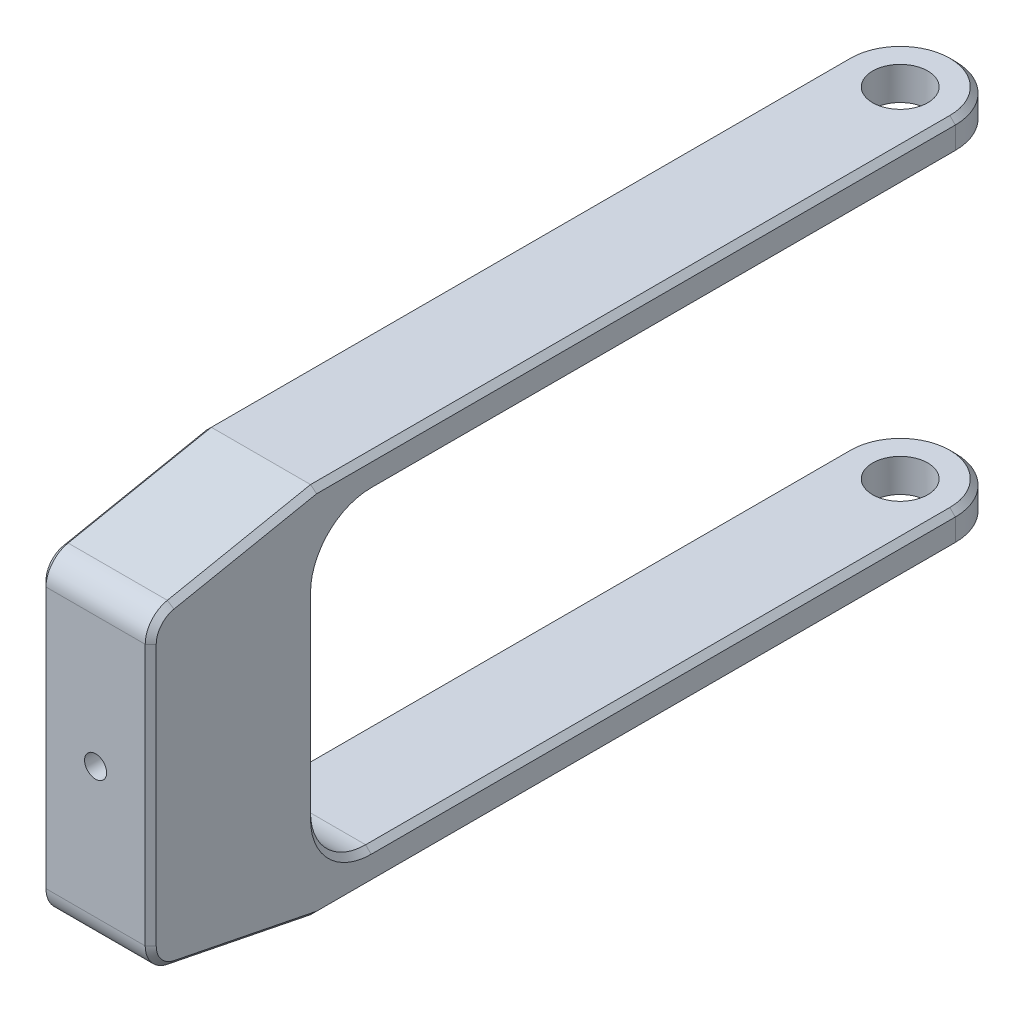
SolidWorks part; units mm, degrees
material "ﾒﾗﾐﾝ樹脂"
ref_plane "正面" through (0, 0, 0) normal (0, 0, 1) x (1, 0, 0)
ref_plane "平面" through (0, 0, 0) normal (0, 1, 0) x (1, 0, 0)
ref_plane "右側面" through (0, 0, 0) normal (1, 0, 0) x (0, 0, -1)
sketch "ｽｹｯﾁ1" plane through (0, 0, 0) normal (0, 1, 0) x (1, 0, 0)
  line L0 (0, 0) -> (0, 63)
  line L1 (0, 63) -> (0, 58)
  line L2 (-5, 58) -> (-5, 0)
  line L3 (-5, 0) -> (5, 0)
  line L4 (5, 0) -> (5, 58)
  line L5 (-5, 58) -> (-5, 63)
  line L6 (-5, 63) -> (0, 63)
  line L7 (0, 63) -> (5, 63)
  line L8 (5, 63) -> (5, 58)
  arc A0 (-5, 58) -> (5, 58) centre (0, 58) cw
extrude "ﾎﾞｽ - 押し出し2" add sketch "ｽｹｯﾁ1" along normal blind 33.8 contours A0 L2 L3 L0 | A0 L0 L3 L4 | L5 A0 L6 | L7 A0 L8 region at (-2.476, 0, -30.9736) region at (2.476, 0, -30.9736) region at (-3.8832, 0, -61.8832) region at (3.8832, 0, -61.8832)
sketch "ｽｹｯﾁ2" plane through (-5, 0, 0) normal (-1, 0, 0) x (0, 0, 1)
  line L0 (-63, 0) -> (-63, 3)
  line L1 (-63, 33.8) -> (-63, 0) construction
  line L2 (-63, 3) -> (0, 3)
  line L3 (0, 33.8) -> (0, 0) construction
  line L4 (0, 3) -> (0, 0)
  line L5 (0, 0) -> (-63, 0)
  line L6 (-63, 33.8) -> (-63, 30.8)
  line L7 (-63, 30.8) -> (0, 30.8)
  line L8 (0, 30.8) -> (0, 33.8)
  line L9 (0, 33.8) -> (-63, 33.8)
  line L10 (-63, 3) -> (-63, 30.8)
  line L11 (0, 3) -> (0, 30.8)
  line M2 (0, 0) -> (0, 33.8)
  line M4 (-63, 33.8) -> (-63, 0)
extrude "ｶｯﾄ - 押し出し2" cut sketch "ｽｹｯﾁ2" against normal through all contours L7 L2 M4 M2 region at (-5, 16.9, -31.5)
sketch "ｽｹｯﾁ4" plane through (-5, 0, 0) normal (-1, 0, 0) x (0, 0, 1)
  line L0 (0, 0) -> (0, 33.8)
  line L1 (0, 16.9) -> (15, 16.9)
  line L2 (0, 3) -> (15, 3)
  line L3 (0, 30.8) -> (15, 30.8)
  line L4 (15, 30.8) -> (15, 3)
  line L5 (0, 0) -> (15, 3)
  line L6 (15, 30.8) -> (0, 33.8)
extrude "ﾎﾞｽ - 押し出し4" add sketch "ｽｹｯﾁ4" against normal up to surface (10 mm away) contours L0 L5 L2 | L4 L1 L0 L2 | L4 L3 L0 L1 | L3 L6 L0 region at (-5, 2, 5) region at (-5, 9.95, 7.5) region at (-5, 23.85, 7.5) region at (-5, 31.8, 5) up to face at (5, 32.3, -31.5)
fillet "ﾌｨﾚｯﾄ1" radius 5 4 edges at (5, 1.5, -63) (-5, 1.5, -63) (5, 32.3, -63) (-5, 32.3, -63)
fillet "ﾌｨﾚｯﾄ2" radius 5 2 edges at (0, 3, 0)
fillet "ﾌｨﾚｯﾄ3" radius 2.5 2 edges at (0, 30.8, 15) (0, 3, 15)
sketch "ｽｹｯﾁ5" plane through (0, 33.8, 0) normal (0, 1, 0) x (1, 0, 0)
  line L0 (0, 63) -> (0, 58)
  circle A0 centre (0, 58) radius 2.5
extrude "ｶｯﾄ - 押し出し3" cut sketch "ｽｹｯﾁ5" against normal through all contours A0 region at (-1.7178, 33.8, -56.2822)
sketch "ｽｹｯﾁ6" plane through (0, 0, 0) normal (0, 0, -1) x (-1, 0, 0)
  circle A0 centre (0, 16.9) radius 1
extrude "ｶｯﾄ - 押し出し4" cut sketch "ｽｹｯﾁ6" against normal through all
chamfer "面取り2" distance 0.5 angle 45 32 edges at (-3.5355, 0, -61.5355) (-5, 0, -29) (-5, 1.299, 6.4951) (-5, 3.4645, 14.4334) (-5, 16.9, 15) (-5, 30.3355, 14.4334) (-5, 32.501, 6.4951) (-5, 33.8, -29) (-3.5355, 33.8, -61.5355) (3.5355, 33.8, -61.5355) (5, 33.8, -29) (5, 32.501, 6.4951) (5, 30.3355, 14.4334) (5, 16.9, 15) (5, 3.4645, 14.4334) (5, 1.299, 6.4951) (5, 0, -29) (3.5355, 0, -61.5355) (3.5355, 3, -61.5355) (-3.5355, 3, -61.5355) (5, 3, -31.5) (5, 4.4645, -1.4645) (-5, 3, -31.5) (-5, 4.4645, -1.4645) (5, 29.3355, -1.4645) (-5, 29.3355, -1.4645) (-3.5355, 30.8, -61.5355) (3.5355, 30.8, -61.5355)
